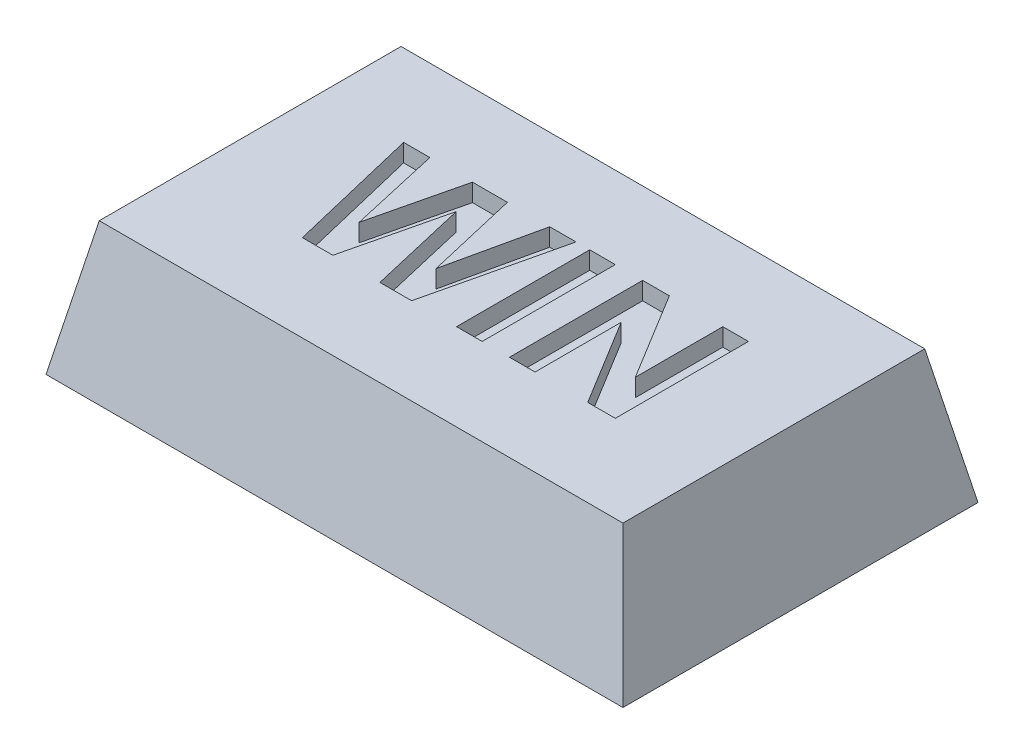
SolidWorks part; units mm, degrees
ref_plane "Front Plane" through (0, 0, 0) normal (0, 0, 1) x (1, 0, 0)
ref_plane "Top Plane" through (0, 0, 0) normal (0, 1, 0) x (1, 0, 0)
ref_plane "Right Plane" through (0, 0, 0) normal (1, 0, 0) x (0, 0, -1)
sketch "Sketch1" plane through (0, 0, 0) normal (0, 1, 0) x (1, 0, 0)
  line L1 (0, 0) -> (13, 0)
  line L2 (0, 0) -> (0, 8)
  line L3 (0, 8) -> (13, 8)
  line L4 (13, 0) -> (13, 8)
  dimension "D1" = 8
  dimension "D2" = 13
extrude "Boss-Extrude1" add sketch "Sketch1" along normal blind 3
sketch "Sketch2" plane through (0, 0, 0) normal (0, 0, 1) x (1, 0, 0)
  line L0 (0, 0) -> (0.6, 3)
  line L1 (0, 3) -> (13, 3) construction
  line L2 (0.6, 3) -> (0, 3)
  line L3 (0, 3) -> (0, 0)
  line L4 (13, 0) -> (12.4, 3)
  line L5 (12.4, 3) -> (13, 3)
  line L6 (13, 3) -> (13, 0)
  dimension "D1" = 0.6
  dimension "D2" = 0.6
extrude "Cut-Extrude1" cut sketch "Sketch2" against normal through all both and the other way through all
sketch "Sketch3" plane through (0, 0, 0) normal (1, 0, 0) x (0, 0, -1)
  line L0 (0, 0) -> (0.6, 3)
  line L1 (8, 3) -> (0, 3) construction
  line L2 (0.6, 3) -> (0, 3)
  line L3 (0, 3) -> (0, 0)
  line L4 (8, 3) -> (7.4, 3)
  line L5 (7.4, 3) -> (8, 0)
  line L6 (8, 3) -> (8, 0)
  dimension "D1" = 0.6
  dimension "D2" = 0.6
extrude "Cut-Extrude2" cut sketch "Sketch3" along normal through all both and the other way through all
sketch "Sketch4" plane through (0, 0, 0) normal (0, -1, 0) x (1, 0, 0)
  line L1 (6.5, 0) -> (6.5, -8) construction
  line L2 (13, -8) -> (0, -8) construction
  line L3 (0, 0) -> (13, 0) construction
  circle A0 centre (6.5, -3.75) radius 1.8
  dimension "D1" = 3.6
  dimension "D2" = 0
  dimension "D3" = 3.75
extrude "Cut-Extrude3" cut sketch "Sketch4" against normal blind 0.8
sketch "Sketch5" plane through (0, 0, 0) normal (0, -1, 0) x (1, 0, 0)
  line L5 (0, 0) -> (13, 0) construction
  line L6 (2.5, -8) -> (10.5, -8)
  line L7 (2.5, -8) -> (2.5, -6.9)
  line L8 (2.5, -6.9) -> (10.5, -6.9)
  line L9 (10.5, -8) -> (10.5, -6.9)
  point P2 (6.5, 0)
  dimension "D1" = 1.1
  dimension "D2" = 4
  dimension "D3" = 4
extrude "Boss-Extrude2" add sketch "Sketch5" along normal blind 2
fillet "Fillet1" radius 4 2 edges at (10.5, -2, -7.45) (2.5, -2, -7.45)
sketch "Sketch6" plane through (0, 3, 0) normal (0, 1, 0) x (1, 0, 0)
  text T0 "WIN" font "Arial" height 3
extrude "Cut-Extrude4" cut sketch "Sketch6" against normal blind 0.4
